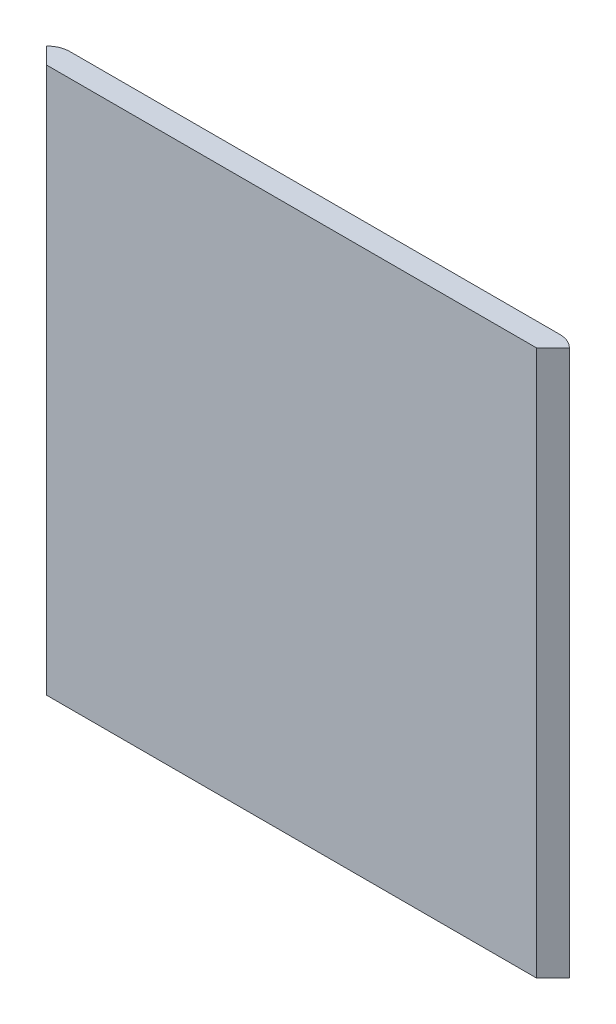
SolidWorks part; units mm, degrees
ref_plane "Front Plane" through (0, 0, 0) normal (0, 0, 1) x (1, 0, 0)
ref_plane "Top Plane" through (0, 0, 0) normal (0, 1, 0) x (1, 0, 0)
ref_plane "Right Plane" through (0, 0, 0) normal (1, 0, 0) x (0, 0, -1)
sketch "Sketch1" plane through (0, 0, 0) normal (0, 0, 1) x (1, 0, 0)
  line L1 (-52.5, -58.5) -> (52.5, -58.5)
  line L2 (-52.5, -58.5) -> (-52.5, 58.5)
  line L3 (-52.5, 58.5) -> (52.5, 58.5)
  line L4 (52.5, -58.5) -> (52.5, 58.5)
  line L5 (-52.5, -58.5) -> (52.5, 58.5) construction
  line L6 (-52.5, 58.5) -> (52.5, -58.5) construction
  point P0 (0, 0)
  dimension "D1" = 105
  dimension "D2" = 117
extrude "Boss-Extrude1" add sketch "Sketch1" along normal blind 5
sketch "Sketch2" plane through (0, -58.5, 0) normal (0, -1, 0) x (1, 0, 0)
  line L0 (-56.0355, 1.4645) -> (-52.5, 5)
  line L1 (-52.5, 5) -> (-57.5, 5) construction
  line L2 (-52.5, 5) -> (-52.5, 0)
  line L3 (-52.5, 0) -> (-57.5, 0) construction
  line L4 (-57.5, 5) -> (-57.5, 0) construction
  line L5 (-52.5, 5) -> (-57.5, 0) construction
  line L6 (-52.5, 0) -> (-57.5, 5) construction
  line L8 (-52.5, 0) -> (52.5, 0) construction
  line L11 (-57.5, 5) -> (-57.5, 15) construction
  line L12 (-57.5, 15) -> (-52.5, 15) construction
  line L13 (-52.5, 5) -> (-52.5, 15) construction
  line L14 (-57.5, 5) -> (-52.5, 15) construction
  line L15 (-57.5, 15) -> (-52.5, 5) construction
  arc A1 (-57.5, 5) -> (-52.5, 0) centre (-52.5, 5) ccw construction
  arc A2 (-52.5, 0) -> (-56.0355, 1.4645) centre (-52.5, 5) cw
  point P5 (-55, 2.5)
  point P8 (-55, 10)
  point P10 (-56.0355, 1.4645)
  line M5 (-52.5, 5) -> (-52.5, 0)
  dimension "D1" = 5
  dimension "D2" = 10
ref_plane "Plane1" through (0, 0, 0) normal (-1, 0, 0) x (0, 0, 1)
extrude "Boss-Extrude2" add sketch "Sketch2" against normal up to surface (117 mm away) separate body contours A2 L0 M5 region at (-53.7431, -58.5, 1.9989) up to face at (0, 58.5, 2.5)
mirror "Mirror1" about plane through (0, 0, 0) normal (-1, 0, 0) of bodies 102
combine bodies "Combine1" operation type add bodies to combine 102 103 101
